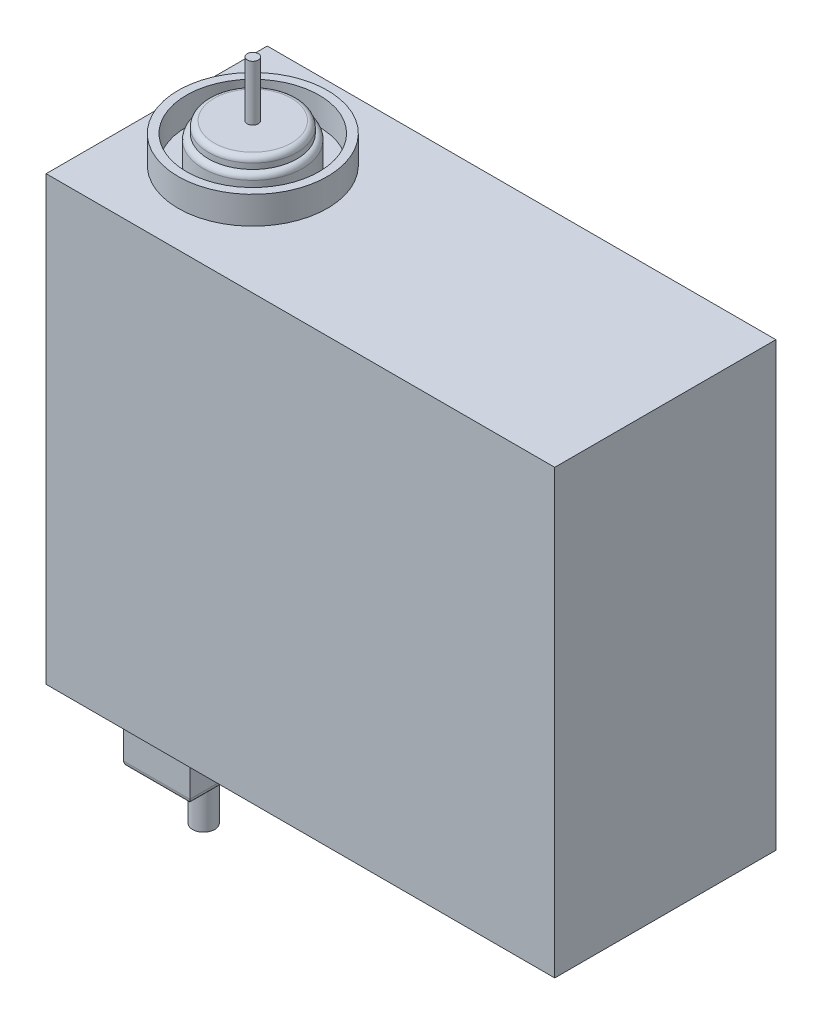
SolidWorks part; units mm, degrees
ref_plane "Front Plane" through (0, 0, 0) normal (0, 0, 1) x (1, 0, 0)
ref_plane "Top Plane" through (0, 0, 0) normal (0, 1, 0) x (1, 0, 0)
ref_plane "Right Plane" through (0, 0, 0) normal (1, 0, 0) x (0, 0, -1)
sketch "Sketch1" plane through (0, 0, 0) normal (0, 1, 0) x (1, 0, 0)
  line L1 (-54.1814, 26.9708) -> (-8.1814, 26.9708)
  line L2 (-54.1814, 26.9708) -> (-54.1814, 6.9708)
  line L3 (-54.1814, 6.9708) -> (-8.1814, 6.9708)
  line L4 (-8.1814, 26.9708) -> (-8.1814, 6.9708)
  dimension "D1" = 46
  dimension "D2" = 20
extrude "Boss-Extrude1" add sketch "Sketch1" along normal blind 40
sketch "Sketch2" plane through (0, 40, 0) normal (0, 1, 0) x (1, 0, 0)
  line L0 (-54.1814, 16.9708) -> (-8.1814, 16.9708) construction
  line L1 (-54.1814, 26.9708) -> (-54.1814, 6.9708) construction
  line L2 (-8.1814, 6.9708) -> (-8.1814, 26.9708) construction
  circle A0 centre (-45.4896, 16.9708) radius 6.75
  circle A1 centre (-45.4896, 16.9708) radius 6
  circle A2 centre (-45.4896, 16.9708) radius 4.5
  dimension "D1" = 13.5
  dimension "D2" = 12
  dimension "D3" = 9
extrude "Boss-Extrude2" add sketch "Sketch2" along normal blind 2.5 contours A2 L0 | L0 A2 | A0 L0 A1 | L0 A0 A1 region at (-45.4896, 40, -15.061) region at (-45.4896, 40, -18.8807) region at (-45.4896, 40, -23.1218) region at (-39.1146, 40, -16.8199)
sketch "Sketch3" plane through (0, 42.5, 0) normal (0, 1, 0) x (1, 0, 0)
  line L0 (-49.9896, 16.9708) -> (-40.9896, 16.9708) construction
  circle A0 centre (-45.4896, 16.9708) radius 4.5 construction
  circle A1 centre (-45.4896, 16.9708) radius 4
  dimension "D1" = 8
extrude "Boss-Extrude3" add sketch "Sketch3" along normal blind 1
fillet "Fillet3" radius 0.5 1 edges at (-45.4896, 43.5, -12.9708)
fillet "Fillet4" radius 0.5 1 edges at (-45.4896, 42.5, -12.4708)
sketch "Sketch5" plane through (0, 43.5, 0) normal (0, 1, 0) x (1, 0, 0)
  line L0 (-48.9896, 16.9708) -> (-41.9896, 16.9708) construction
  circle A0 centre (-45.4896, 16.9708) radius 3.5 construction
  circle A1 centre (-45.4896, 16.9708) radius 0.5
  dimension "D1" = 1
extrude "Boss-Extrude4" add sketch "Sketch5" along normal blind 5
sketch "Sketch6" plane through (0, 0, 0) normal (0, -1, 0) x (1, 0, 0)
  line L0 (-54.1814, -26.9708) -> (-54.1814, -6.9708) construction
  line L1 (-49.1814, -8.9708) -> (-43.1814, -8.9708)
  line L2 (-49.1814, -8.9708) -> (-49.1814, -24.9708)
  line L3 (-49.1814, -24.9708) -> (-43.1814, -24.9708)
  line L4 (-43.1814, -8.9708) -> (-43.1814, -24.9708)
  line L5 (-54.1814, -6.9708) -> (-8.1814, -6.9708) construction
  line L6 (-8.1814, -26.9708) -> (-54.1814, -26.9708) construction
  dimension "D1" = 5
  dimension "D2" = 6
  dimension "D3" = 2
  dimension "D4" = 2
extrude "Boss-Extrude5" add sketch "Sketch6" along normal blind 5
fillet "Fillet5" radius 0.5 4 edges at (-46.1814, -5, -8.9708) (-43.1814, -5, -16.9708) (-46.1814, -5, -24.9708) (-49.1814, -5, -16.9708)
sketch "Sketch7" plane through (0, -5, 0) normal (0, -1, 0) x (-1, 0, 0)
  line L0 (46.1814, 9.4708) -> (46.1814, 24.4708) construction
  line L1 (43.6814, 9.4708) -> (48.6814, 9.4708) construction
  line L2 (48.6814, 24.4708) -> (43.6814, 24.4708) construction
  line L3 (46.1814, 24.4708) -> (46.1814, 16.9708) construction
  line L4 (46.1814, 16.9708) -> (46.1814, 9.4708) construction
  line L5 (46.1814, 24.4708) -> (46.1814, 16.9708) construction
  line L6 (46.1814, 16.9708) -> (46.1814, 9.4708) construction
  line L7 (46.1814, 16.9708) -> (46.1814, 24.4708) construction
  circle A0 centre (46.1814, 13.2208) radius 1
  circle A1 centre (46.1814, 20.7208) radius 1
  dimension "D1" = 2
  dimension "D2" = 2
extrude "Boss-Extrude6" add sketch "Sketch7" along normal blind 5
